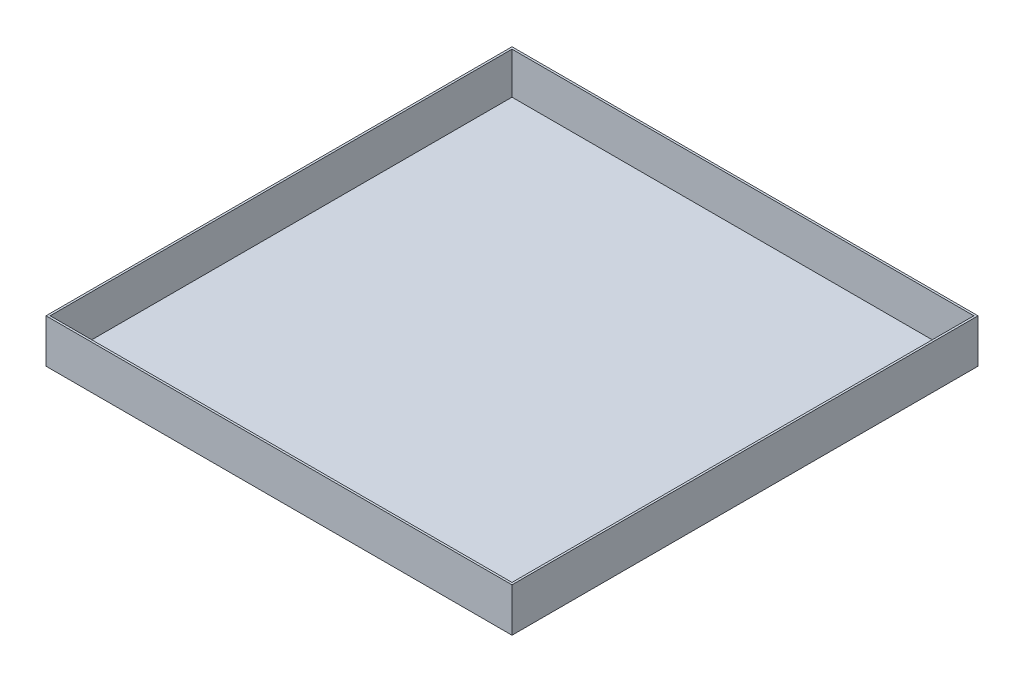
SolidWorks part; units mm, degrees
ref_plane "Front" through (0, 0, 0) normal (0, 0, 1) x (1, 0, 0)
ref_plane "Top" through (0, 0, 0) normal (0, 1, 0) x (1, 0, 0)
ref_plane "Right" through (0, 0, 0) normal (1, 0, 0) x (0, 0, -1)
sketch "Croquis1" plane through (0, 0, 0) normal (0, 1, 0) x (1, 0, 0)
  line L1 (-112, 112) -> (112, 112)
  line L2 (-112, 112) -> (-112, -112)
  line L3 (-112, -112) -> (112, -112)
  line L4 (112, 112) -> (112, -112)
  line L5 (-112, 112) -> (112, -112) construction
  line L6 (-112, -112) -> (112, 112) construction
  point P0 (0, 0)
  dimension "D1" = 224
  dimension "D2" = 224
extrude "Saliente-Extruir1" add sketch "Croquis1" along normal blind 1
sketch "Croquis3" plane through (0, 1, 0) normal (0, 1, 0) x (1, 0, 0)
  line L0 (-112, -112) -> (112, -112) construction
  line L2 (112, 112) -> (112, -112)
  line L3 (112, -112) -> (-112, -112)
  line L4 (-112, 112) -> (-112, -112)
  line L5 (112, 112) -> (-112, -112) construction
  line L6 (112, -112) -> (-112, 112) construction
  line L8 (112, 112) -> (-112, 112)
  line L9 (112, 112) -> (112, -112)
  line L10 (112, -112) -> (-112, -112)
  line L11 (-112, 112) -> (-112, -112)
  line L12 (112, 112) -> (-112, -112) construction
  line L13 (112, -112) -> (-112, 112) construction
  line L14 (111, 111) -> (-111, 111)
  line L15 (111, 111) -> (111, -111)
  line L16 (111, -111) -> (-111, -111)
  line L17 (-111, 111) -> (-111, -111)
  line L18 (111, 111) -> (-111, -111) construction
  line L19 (111, -111) -> (-111, 111) construction
  point P0 (0, 0)
  point P8 (0, 0)
  point P9 (0, 0)
  line M1 (112, -112) -> (112, 112)
  line M2 (112, 112) -> (-112, 112)
  line M3 (-112, 112) -> (-112, -112)
  line M4 (-112, -112) -> (112, -112)
  dimension "D1" = 224
  dimension "D2" = 222
extrude "Saliente-Extruir2" add sketch "Croquis3" along normal blind 20 contours L17 L14 L15 L16 M4 M1 M2 M3 region at (111.6832, 1, 0)
